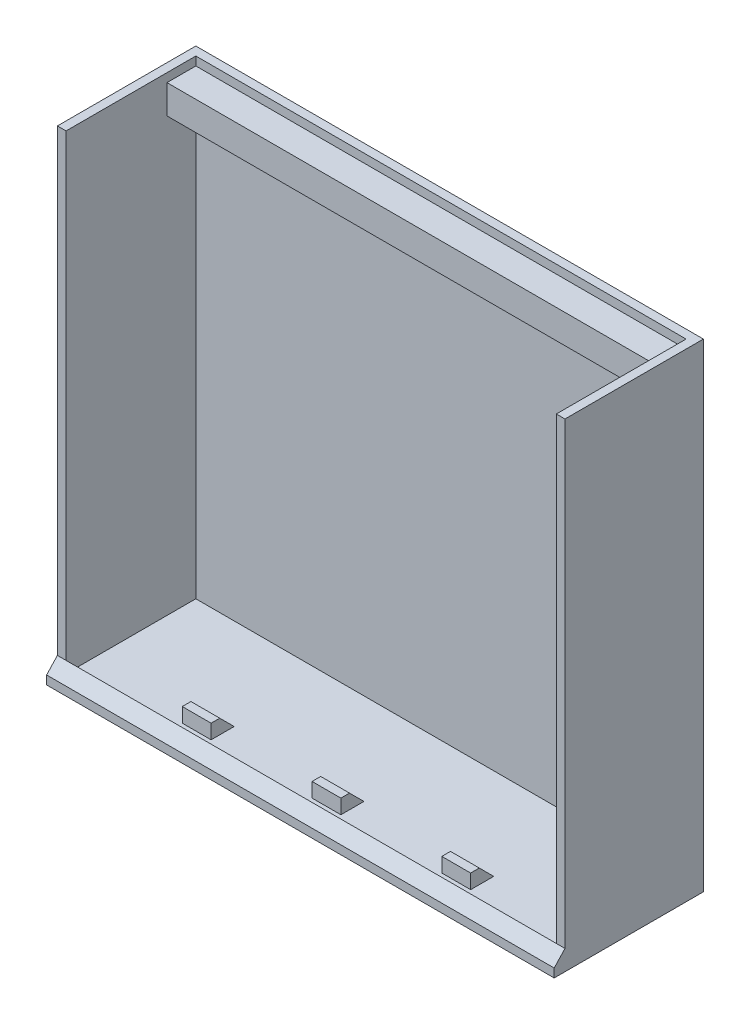
SolidWorks part; units mm, degrees
ref_plane "Front Plane" through (0, 0, 0) normal (0, 0, 1) x (1, 0, 0)
ref_plane "Top Plane" through (0, 0, 0) normal (0, 1, 0) x (1, 0, 0)
ref_plane "Right Plane" through (0, 0, 0) normal (1, 0, 0) x (0, 0, -1)
sketch "Sketch1" plane through (0, 0, 0) normal (1, 0, 0) x (0, 0, -1)
  line L0 (0, 163) -> (3, 163)
  line L1 (0, 0) -> (-45, 0)
  line L2 (0, 0) -> (0, 163)
  line L3 (0, 163) -> (-45, 163)
  line L4 (-45, 0) -> (-45, 163)
  line L5 (3, 163) -> (3, -3)
  line L6 (3, -3) -> (-45, -3)
  line L7 (-45, -3) -> (-45, 0)
  dimension "D1" = 163
  dimension "D2" = 45
  dimension "D3" = 3
  dimension "D4" = 3
extrude "Boss-Extrude1" add sketch "Sketch1" along normal blind 85 and the other way blind 85 contours L7 L6 L5 L0 L2 L1 region at (0, 161.272, -1.5)
extrude "Boss-Extrude2" add sketch "Sketch1<4>" against normal blind 3 from surface contours L4 L1 L2 L3 | L7 L6 L5 L0 L2 L1 region at (0, 161.272, -1.5) region at (0, 81.5, 22.5) starting at face at (-85, 53.3333, 14)
sketch "Sketch1<4>" plane through (0, 0, 0) normal (1, 0, 0) x (0, 0, -1) same geometry as "Sketch1"
extrude "Boss-Extrude3" add sketch "Sketch1<5>" along normal blind 3 from surface contours L7 L6 L5 L0 L2 L1 | L4 L1 L2 L3 region at (0, 161.272, -1.5) region at (0, 81.5, 22.5) starting at face at (85, 53.3333, 14)
sketch "Sketch1<5>" plane through (0, 0, 0) normal (1, 0, 0) x (0, 0, -1) same geometry as "Sketch1"
sketch "Sketch2" plane through (0, 0, 0) normal (1, 0, 0) x (0, 0, -1)
  line L0 (-10, 160) -> (-10, 150)
  line L2 (-10, 150) -> (0, 140)
  line L3 (0, 0) -> (0, 163) construction
  line L4 (0, 140) -> (0, 160)
  line L7 (-10, 160) -> (0, 160)
  line L8 (0, 160) -> (0, 163) construction
  dimension "D1" = 10
  dimension "D2" = 10
  dimension "D3" = 20
  dimension "D4" = 3
extrude "Boss-Extrude4" add sketch "Sketch2" along normal through all and the other way through all
sketch "Sketch4" plane through (0, 0, 0) normal (1, 0, 0) x (0, 0, -1)
  line L0 (-45, -3) -> (-48.7426, -3)
  line L1 (-48.7426, -3) -> (-48.7426, 0)
  line L2 (-48.7426, 0) -> (-45, 4)
  line L3 (-45, 0) -> (-45, 163) construction
  line L4 (-45, 4) -> (-45, 0)
  line L5 (-45, -3) -> (-45, 0)
  point P3 (0, 0)
  point P9 (0, 0)
  dimension "D1" = 4
sketch "Sketch5" plane through (0, 0, 0) normal (0, 1, 0) x (1, 0, 0)
  line L1 (-40, -39.7) -> (-50, -39.7)
  line L2 (-40, -39.7) -> (-40, -36.7)
  line L3 (-40, -36.7) -> (-50, -36.7)
  line L4 (-50, -39.7) -> (-50, -36.7)
  line L5 (50, -36.7) -> (40, -36.7)
  line L6 (50, -36.7) -> (50, -39.7)
  line L7 (50, -39.7) -> (40, -39.7)
  line L8 (40, -36.7) -> (40, -39.7)
  line L9 (-5, 0) -> (-85, -45) construction
  line L10 (5, 0) -> (85, -45) construction
  line L11 (85, 0) -> (-85, 0) construction
  line L12 (-85, 0) -> (85, 0) construction
  line L13 (-85, -45) -> (85, -45) construction
  line L14 (5, -39.7) -> (-5, -39.7)
  line L15 (5, -39.7) -> (5, -36.7)
  line L16 (5, -36.7) -> (-5, -36.7)
  line L17 (-5, -39.7) -> (-5, -36.7)
  point P14 (-45, -22.5)
  point P15 (-45, -36.7)
  point P23 (45, -36.7)
  point P24 (45, -22.5)
  point P25 (0, -36.7)
  point P26 (0, 0)
  point P32 (0, 0)
  point P33 (-39.9664, -39.7)
  point P35 (0, 0)
  point P36 (0, 0)
  point P37 (5.2173, 0.6248)
  point P38 (0, 0)
  dimension "D1" = 10
  dimension "D2" = 10
  dimension "D3" = 5.3
  dimension "D4" = 3
  dimension "D5" = 10
  dimension "D6" = 5
  dimension "D7" = 5
extrude "Boss-Extrude7" add sketch "Sketch5" along normal blind 5
extrude "Boss-Extrude8" add sketch "Sketch4" along normal through all and the other way through all
chamfer "Chamfer1" distance 5 angle 45 3 edges at (0, 0, 36.7) (45, 0, 36.7) (-45, 0, 36.7)
equation "\"D1@Boss-Extrude1\"=80+5"
equation "\"D2@Boss-Extrude1\"=80+5"
